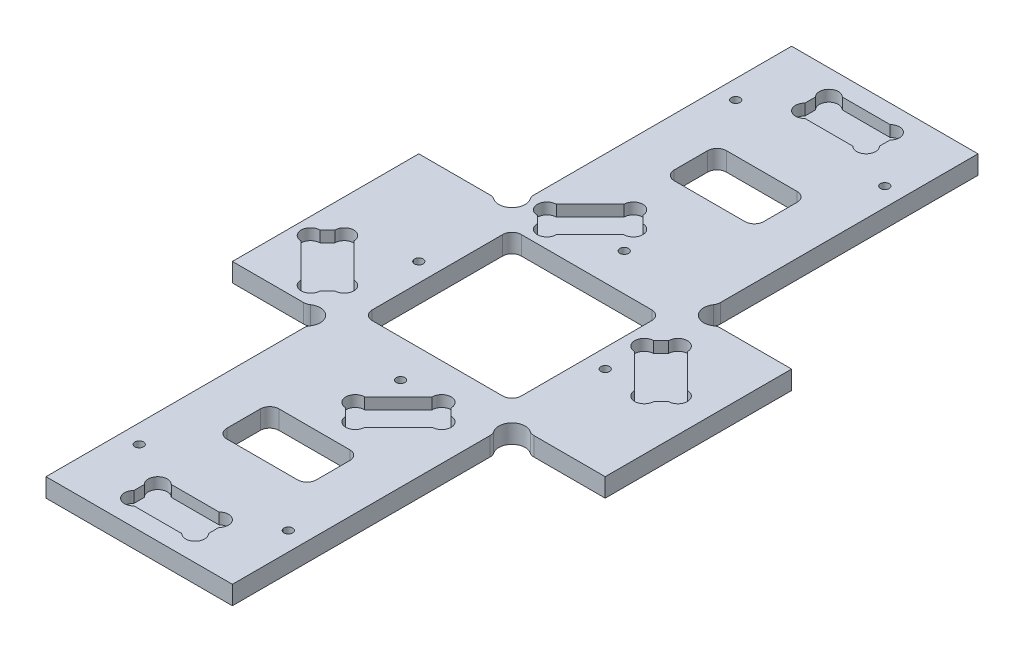
SolidWorks part; units mm, degrees
ref_plane "Front" through (0, 0, 0) normal (0, 0, 1) x (1, 0, 0)
ref_plane "Top" through (0, 0, 0) normal (0, 1, 0) x (1, 0, 0)
ref_plane "Right" through (0, 0, 0) normal (1, 0, 0) x (0, 0, -1)
sketch "Sketch1" plane through (0, 0, 0) normal (0, 1, 0) x (1, 0, 0)
  line L0 (45.4057, 247.3952) -> (45.4057, -6.6048) construction
  line L1 (13.6557, -6.6048) -> (77.1557, -6.6048)
  line L2 (13.6557, -6.6048) -> (13.6557, 247.3952)
  line L3 (13.6557, 247.3952) -> (77.1557, 247.3952)
  line L4 (77.1557, -6.6048) -> (77.1557, 247.3952)
  line L5 (13.6557, 152.1452) -> (-18.0943, 152.1452)
  line L6 (13.6557, 152.1452) -> (13.6557, 88.6452)
  line L7 (13.6557, 88.6452) -> (-18.0943, 88.6452)
  line L8 (-18.0943, 152.1452) -> (-18.0943, 88.6452)
  line L9 (77.1557, 88.6452) -> (108.9057, 88.6452)
  line L10 (108.9057, 152.1452) -> (108.9057, 88.6452)
  line L11 (77.1557, 152.1452) -> (108.9057, 152.1452)
  line L12 (77.1557, 152.1452) -> (77.1557, 88.6452)
  dimension "D1" = 63.5
  dimension "D2" = 254
  dimension "D3" = 31.75
  dimension "D4" = 63.5
  dimension "D5" = 95.25
extrude "Boss-Extrude1" add sketch "Sketch1" along normal blind 6.35 contours L5 L8 L7 L2 | L0 L3 L2 L1 | L3 L0 L1 L4 | L11 L4 L9 L10 region at (61.2807, 0, -120.3952) region at (29.5307, 0, -120.3952) region at (-2.2193, 0, -120.3952) region at (93.0307, 0, -120.3952)
sketch "Sketch2" plane through (0, 6.35, 0) normal (0, 1, 0) x (1, 0, 0)
  line L0 (13.6557, 88.6452) -> (77.1557, 152.1452) construction
  line L1 (77.1557, 152.1452) -> (77.1557, 88.6452) construction
  line L2 (77.1557, 88.6452) -> (45.4057, 120.3952) construction
  line L3 (45.4057, 120.3952) -> (45.4057, 152.1452) construction
  line L4 (45.4057, 152.1452) -> (13.6557, 152.1452) construction
  line L5 (13.6557, 152.1452) -> (45.4057, 120.3952) construction
  line L6 (2.3005, 109.6188) -> (-6.6798, 100.6386) construction
  line L7 (11.2807, 100.6386) -> (-6.6798, 118.5991)
  line L8 (-6.6798, 118.5991) -> (11.2807, 100.6386)
  line L9 (-6.6798, 118.5991) -> (-15.6601, 109.6188)
  line L10 (11.2807, 100.6386) -> (2.3005, 91.6583)
  line L11 (-15.6601, 109.6188) -> (2.3005, 91.6583)
  line L23 (11.2807, 100.6386) -> (2.3005, 91.6583)
  line L28 (43.9231, 166.4458) -> (25.9626, 148.4853)
  line L29 (43.9231, 166.4458) -> (34.9428, 175.4261)
  line L30 (34.9428, 175.4261) -> (16.9823, 157.4655)
  line L31 (25.9626, 148.4853) -> (16.9823, 157.4655)
  line L36 (43.9231, 166.4458) -> (34.9428, 175.4261)
  line L38 (6.7906, 96.1485) -> (-11.1699, 114.109) construction
  line L43 (91.7698, 115.8429) -> (73.8093, 133.8034)
  line L44 (91.7698, 115.8429) -> (100.7501, 124.8232)
  line L45 (100.7501, 124.8232) -> (82.7895, 142.7837)
  line L46 (73.8093, 133.8034) -> (82.7895, 142.7837)
  line L51 (91.7698, 115.8429) -> (100.7501, 124.8232)
  line L58 (41.1669, 67.9962) -> (59.1274, 85.9567)
  line L59 (41.1669, 67.9962) -> (50.1472, 59.0159)
  line L60 (50.1472, 59.0159) -> (68.1077, 76.9765)
  line L61 (59.1274, 85.9567) -> (68.1077, 76.9765)
  line L66 (41.1669, 67.9962) -> (50.1472, 59.0159)
  point P15 (2.3005, 109.6188)
  point P64 (42.545, 117.221)
  dimension "D1" = 22.86
  dimension "D2" = 25.4
  dimension "D3" = 12.7
  dimension "D7" = 38.1
  dimension "D6" = 4
extrude "Cut-Extrude14" cut sketch "Sketch2" against normal blind 3.81 contours L9 L11 L10 L7 | L31 L28 L29 L30 | L46 L43 L44 L45 | L61 L58 L59 L60 region at (-2.1897, 6.35, -105.1287) region at (30.4527, 6.35, -161.9557) region at (87.2797, 6.35, -129.3133) region at (54.6373, 6.35, -72.4863)
sketch "Sketch14" plane through (0, 6.35, 0) normal (0, 1, 0) x (1, 0, 0)
  line L0 (45.4057, -6.6048) -> (45.4057, 247.3952) construction
  line L1 (13.6557, -6.6048) -> (77.1557, -6.6048) construction
  line L2 (13.6557, 247.3952) -> (77.1557, 247.3952) construction
  line L3 (-18.0943, 120.3952) -> (108.9057, 120.3952) construction
  line L4 (32.7057, 241.0452) -> (58.1057, 241.0452)
  line L5 (32.7057, 241.0452) -> (32.7057, 228.3452)
  line L6 (32.7057, 228.3452) -> (58.1057, 228.3452)
  line L7 (58.1057, 241.0452) -> (58.1057, 228.3452)
  line L8 (32.7057, 241.0452) -> (58.1057, 228.3452) construction
  line L9 (32.7057, 228.3452) -> (58.1057, 241.0452) construction
  line L10 (-18.0943, 152.1452) -> (-18.0943, 88.6452) construction
  line L11 (108.9057, 152.1452) -> (108.9057, 88.6452) construction
  line L12 (32.7057, 12.4452) -> (58.1057, 12.4452)
  line L13 (58.1057, -0.2548) -> (58.1057, 12.4452)
  line L14 (32.7057, -0.2548) -> (58.1057, -0.2548)
  line L15 (32.7057, -0.2548) -> (32.7057, 12.4452)
  point P6 (45.4057, 234.6952)
  dimension "D1" = 12.7
  dimension "D2" = 25.4
  dimension "D3" = 6.35
extrude "Cut-Extrude16" cut sketch "Sketch14" against normal blind 3.81
sketch "Sketch15" plane through (0, 6.35, 0) normal (0, 1, 0) x (1, 0, 0)
  line L0 (45.4057, 247.3952) -> (45.4057, -6.6048) construction
  line L1 (13.6557, 247.3952) -> (77.1557, 247.3952) construction
  line L2 (13.6557, -6.6048) -> (77.1557, -6.6048) construction
  line L3 (45.4057, -6.6048) -> (108.9057, 120.3952) construction
  line L4 (108.9057, 152.1452) -> (108.9057, 88.6452) construction
  line L5 (108.9057, 120.3952) -> (-18.0943, 120.3952) construction
  line L6 (-18.0943, 152.1452) -> (-18.0943, 88.6452) construction
  line L7 (30.1657, 35.3052) -> (60.6457, 35.3052)
  line L8 (20.0057, 94.9952) -> (70.8057, 94.9952)
  line L9 (20.0057, 94.9952) -> (20.0057, 145.7952)
  line L10 (20.0057, 145.7952) -> (70.8057, 145.7952)
  line L11 (70.8057, 94.9952) -> (70.8057, 145.7952)
  line L12 (20.0057, 94.9952) -> (70.8057, 145.7952) construction
  line L13 (20.0057, 145.7952) -> (70.8057, 94.9952) construction
  line L14 (30.1657, 187.7052) -> (60.6457, 187.7052)
  line L15 (30.1657, 187.7052) -> (30.1657, 205.4852)
  line L16 (30.1657, 205.4852) -> (60.6457, 205.4852)
  line L17 (60.6457, 187.7052) -> (60.6457, 205.4852)
  line L18 (30.1657, 187.7052) -> (60.6457, 205.4852) construction
  line L19 (30.1657, 205.4852) -> (60.6457, 187.7052) construction
  line L20 (60.6457, 53.0852) -> (60.6457, 35.3052)
  line L21 (30.1657, 53.0852) -> (60.6457, 53.0852)
  line L22 (30.1657, 53.0852) -> (30.1657, 35.3052)
  point P6 (45.4057, 120.3952)
  point P17 (45.4057, 196.5952)
  dimension "D1" = 50.8
  dimension "D2" = 50.8
  dimension "D3" = 17.78
  dimension "D4" = 30.48
  dimension "D5" = 50.8
extrude "Cut-Extrude17" cut sketch "Sketch15" against normal through all
fillet "Fillet1" radius 3.175 12 edges at (30.1657, 3.175, -205.4852) (30.1657, 3.175, -187.7052) (60.6457, 3.175, -187.7052) (60.6457, 3.175, -205.4852) (60.6457, 3.175, -53.0852) (30.1657, 3.175, -53.0852) (30.1657, 3.175, -35.3052) (60.6457, 3.175, -35.3052) (70.8057, 3.175, -94.9952) (70.8057, 3.175, -145.7952) (20.0057, 3.175, -145.7952) (20.0057, 3.175, -94.9952)
sketch "Sketch16" plane through (0, 6.35, 0) normal (0, 1, 0) x (1, 0, 0)
  line L0 (45.4057, -6.6048) -> (45.4057, 247.3952) construction
  line L1 (13.6557, 88.6452) -> (10.4807, 88.6452)
  line L2 (13.6557, 88.6452) -> (13.6557, 85.4702)
  line L3 (13.6557, 85.4702) -> (10.4807, 85.4702)
  line L4 (10.4807, 88.6452) -> (10.4807, 85.4702)
  line L5 (13.6557, -6.6048) -> (77.1557, -6.6048) construction
  line L6 (13.6557, 247.3952) -> (77.1557, 247.3952) construction
  line L7 (45.4057, 247.3952) -> (108.9057, 120.3952) construction
  line L8 (108.9057, 152.1452) -> (108.9057, 88.6452) construction
  line L9 (108.9057, 120.3952) -> (-18.0943, 120.3952) construction
  line L10 (-18.0943, 152.1452) -> (-18.0943, 88.6452) construction
  line L11 (77.1557, 85.4702) -> (80.3307, 85.4702)
  line L12 (80.3307, 88.6452) -> (80.3307, 85.4702)
  line L13 (77.1557, 88.6452) -> (80.3307, 88.6452)
  line L14 (77.1557, 88.6452) -> (77.1557, 85.4702)
  line L16 (77.1557, 152.1452) -> (77.1557, 155.3202)
  line L17 (77.1557, 152.1452) -> (80.3307, 152.1452)
  line L18 (80.3307, 152.1452) -> (80.3307, 155.3202)
  line L19 (77.1557, 155.3202) -> (80.3307, 155.3202)
  line L20 (13.6557, 155.3202) -> (10.4807, 155.3202)
  line L21 (10.4807, 152.1452) -> (10.4807, 155.3202)
  line L22 (13.6557, 152.1452) -> (10.4807, 152.1452)
  line L23 (13.6557, 152.1452) -> (13.6557, 155.3202)
  circle A0 centre (10.4807, 85.4702) radius 4.4901
  circle A1 centre (80.3307, 85.4702) radius 4.4901
  circle A2 centre (80.3307, 155.3202) radius 4.4901
  circle A3 centre (10.4807, 155.3202) radius 4.4901
  dimension "D1" = 3.175
  dimension "D2" = 3.175
extrude "Cut-Extrude18" cut sketch "Sketch16" against normal through all contours L1 A0 L2 L3 L4 | L1 L4 L3 L2 | L13 L14 L11 L12 | L14 A1 L13 L12 L11 | L19 L16 L17 L18 | L17 A2 L16 L19 L18 | L22 L23 L20 L21 | L23 A3 L22 L21 L20 region at (12.0682, 6.35, -87.0577) region at (10.1802, 6.35, -85.1697) region at (78.7432, 6.35, -87.0577) region at (80.6312, 6.35, -85.1697) region at (78.7432, 6.35, -153.7327) region at (80.6312, 6.35, -155.6206) region at (12.0682, 6.35, -153.7327) region at (10.1802, 6.35, -155.6206)
fillet "Fillet2" radius 3.175 8 edges at (13.6557, 3.175, -158.4952) (7.3057, 3.175, -152.1452) (77.1557, 3.175, -158.4952) (83.5057, 3.175, -152.1452) (77.1557, 3.175, -82.2952) (83.5057, 3.175, -88.6452) (13.6557, 3.175, -82.2952) (7.3057, 3.175, -88.6452)
sketch "Sketch17" plane through (0, 6.35, 0) normal (0, 1, 0) x (1, 0, 0)
  line L0 (45.4057, -6.6048) -> (45.4057, 247.3952) construction
  line L1 (13.6557, -6.6048) -> (77.1557, -6.6048) construction
  line L2 (13.6557, 247.3952) -> (77.1557, 247.3952) construction
  line L3 (45.4057, 247.3952) -> (108.9057, 120.3952) construction
  line L4 (108.9057, 152.1452) -> (108.9057, 88.6452) construction
  line L5 (108.9057, 120.3952) -> (-18.0943, 120.3952) construction
  line L6 (-18.0943, 152.1452) -> (-18.0943, 88.6452) construction
  line L7 (-18.0943, 120.3952) -> (32.7057, 6.0952) construction
  line L8 (32.7057, 12.4452) -> (32.7057, -0.2548) construction
  line L9 (32.7057, 6.0952) -> (58.1057, 6.0952) construction
  line L10 (58.1057, -0.2548) -> (58.1057, 12.4452) construction
  line L11 (32.7057, 12.4452) -> (34.9917, 12.4452)
  line L12 (32.7057, 12.4452) -> (32.7057, 10.1592)
  line L13 (34.9917, 12.4452) -> (34.9917, 10.1592)
  line L14 (32.7057, 10.1592) -> (34.9917, 10.1592)
  line L15 (58.1057, 12.4452) -> (32.7057, 12.4452) construction
  line L16 (34.9917, -0.2548) -> (34.9917, 2.0312)
  line L17 (32.7057, 2.0312) -> (34.9917, 2.0312)
  line L18 (32.7057, -0.2548) -> (32.7057, 2.0312)
  line L19 (32.7057, -0.2548) -> (34.9917, -0.2548)
  line L20 (58.1057, -0.2548) -> (55.8197, -0.2548)
  line L21 (58.1057, -0.2548) -> (58.1057, 2.0312)
  line L22 (58.1057, 2.0312) -> (55.8197, 2.0312)
  line L23 (55.8197, -0.2548) -> (55.8197, 2.0312)
  line L24 (55.8197, 12.4452) -> (55.8197, 10.1592)
  line L25 (58.1057, 10.1592) -> (55.8197, 10.1592)
  line L26 (58.1057, 12.4452) -> (58.1057, 10.1592)
  line L27 (58.1057, 12.4452) -> (55.8197, 12.4452)
  line L28 (58.1057, 241.0452) -> (58.1057, 238.7592)
  line L29 (58.1057, 238.7592) -> (55.8197, 238.7592)
  line L30 (55.8197, 241.0452) -> (55.8197, 238.7592)
  line L31 (58.1057, 241.0452) -> (55.8197, 241.0452)
  line L32 (58.1057, 228.3452) -> (55.8197, 228.3452)
  line L33 (58.1057, 228.3452) -> (58.1057, 230.6312)
  line L34 (58.1057, 230.6312) -> (55.8197, 230.6312)
  line L35 (55.8197, 228.3452) -> (55.8197, 230.6312)
  line L36 (34.9917, 228.3452) -> (34.9917, 230.6312)
  line L37 (32.7057, 230.6312) -> (34.9917, 230.6312)
  line L38 (32.7057, 228.3452) -> (32.7057, 230.6312)
  line L39 (32.7057, 228.3452) -> (34.9917, 228.3452)
  line L40 (32.7057, 241.0452) -> (34.9917, 241.0452)
  line L41 (32.7057, 241.0452) -> (32.7057, 238.7592)
  line L42 (32.7057, 238.7592) -> (34.9917, 238.7592)
  line L43 (34.9917, 241.0452) -> (34.9917, 238.7592)
  circle A0 centre (34.9917, 10.1592) radius 3.2329
  circle A1 centre (34.9917, 2.0312) radius 3.2329
  circle A2 centre (55.8197, 2.0312) radius 3.2329
  circle A3 centre (55.8197, 10.1592) radius 3.2329
  circle A4 centre (55.8197, 238.7592) radius 3.2329
  circle A5 centre (55.8197, 230.6312) radius 3.2329
  circle A6 centre (34.9917, 230.6312) radius 3.2329
  circle A7 centre (34.9917, 238.7592) radius 3.2329
  dimension "D1" = 2.286
  dimension "D2" = 2.286
extrude "Cut-Extrude19" cut sketch "Sketch17" against normal blind 3.81 contours L43 L40 L41 L42 | L41 A7 L40 L43 L42 | L31 A4 L28 L29 L30 | L28 L31 L30 L29 | L33 A5 L32 L35 L34 | L35 L32 L33 L34 | L39 A6 L38 L37 L36 | L38 L39 L36 L37 | L19 A1 L18 L17 L16 | L18 L19 L16 L17 | L12 A0 L11 L13 L14 | L12 L14 L13 L11 | L27 A3 L26 L25 L24 | L26 L27 L24 L25 | L21 A2 L20 L23 L22 | L23 L20 L21 L22 region at (33.8487, 6.35, -11.3022) region at (35.208, 6.35, -9.9428) region at (33.8487, 6.35, -0.8882) region at (35.208, 6.35, -2.2475) region at (56.9627, 6.35, -0.8882) region at (55.6033, 6.35, -2.2475) region at (56.9627, 6.35, -11.3022) region at (55.6033, 6.35, -9.9428) region at (56.9627, 6.35, -239.9022) region at (55.6033, 6.35, -238.5428) region at (56.9627, 6.35, -229.4882) region at (55.6033, 6.35, -230.8475) region at (33.8487, 6.35, -229.4882) region at (35.208, 6.35, -230.8475) region at (33.8487, 6.35, -239.9022) region at (35.208, 6.35, -238.5428)
sketch "Sketch18" plane through (0, 6.35, 0) normal (0, 1, 0) x (1, 0, 0)
  line L0 (-15.6601, 109.6188) -> (-14.0436, 111.2353)
  line L1 (-15.6601, 109.6188) -> (-14.0436, 108.0024)
  line L2 (-14.0436, 111.2353) -> (-12.4272, 109.6188)
  line L3 (-14.0436, 108.0024) -> (-12.4272, 109.6188)
  line L4 (-6.6798, 118.5991) -> (-15.6601, 109.6188) construction
  line L5 (-11.1699, 114.109) -> (6.7906, 96.1485) construction
  line L6 (11.2807, 100.6386) -> (2.3005, 91.6583) construction
  line L7 (6.7906, 96.1485) -> (2.3005, 109.6188) construction
  line L8 (11.2807, 100.6386) -> (-6.6798, 118.5991) construction
  line L9 (2.3005, 109.6188) -> (-6.6798, 100.6386) construction
  line L10 (-15.6601, 109.6188) -> (2.3005, 91.6583) construction
  line L11 (-8.2962, 116.9827) -> (-6.6798, 115.3662)
  line L12 (-5.0634, 116.9827) -> (-6.6798, 115.3662)
  line L13 (-6.6798, 118.5991) -> (-5.0634, 116.9827)
  line L14 (-6.6798, 118.5991) -> (-8.2962, 116.9827)
  line L15 (11.2807, 100.6386) -> (9.6643, 99.0221)
  line L16 (11.2807, 100.6386) -> (9.6643, 102.255)
  line L17 (9.6643, 102.255) -> (8.0478, 100.6386)
  line L18 (9.6643, 99.0221) -> (8.0478, 100.6386)
  line L19 (3.9169, 93.2748) -> (2.3005, 94.8912)
  line L20 (0.684, 93.2748) -> (2.3005, 94.8912)
  line L21 (2.3005, 91.6583) -> (0.684, 93.2748)
  line L22 (2.3005, 91.6583) -> (3.9169, 93.2748)
  line L23 (45.4057, 145.7952) -> (45.4057, 94.9952) construction
  line L24 (67.6307, 145.7952) -> (23.1807, 145.7952) construction
  line L25 (23.1807, 94.9952) -> (67.6307, 94.9952) construction
  line L26 (45.4057, 94.9952) -> (70.8057, 120.3952) construction
  line L27 (70.8057, 98.1702) -> (70.8057, 142.6202) construction
  line L28 (70.8057, 120.3952) -> (20.0057, 120.3952) construction
  line L29 (20.0057, 142.6202) -> (20.0057, 98.1702) construction
  circle A0 centre (-12.4272, 109.6188) radius 3.2329
  circle A1 centre (-6.6798, 115.3662) radius 3.2329
  circle A2 centre (8.0478, 100.6386) radius 3.2329
  circle A3 centre (2.3005, 94.8912) radius 3.2329
  dimension "D1" = 2.286
  dimension "D2" = 2.286
extrude "Cut-Extrude20" cut sketch "Sketch18" against normal blind 3.81 contours L1 L3 L2 L0 | L1 A0 L0 L2 L3 | L13 L14 L11 L12 | L14 A1 L13 L12 L11 | L18 L15 L16 L17 | L16 A2 L15 L18 L17 | L21 L22 L19 L20 | L22 A3 L21 L20 L19 region at (-14.0436, 6.35, -109.6188) region at (-12.1212, 6.35, -109.6188) region at (-6.6798, 6.35, -116.9827) region at (-6.6798, 6.35, -115.0602) region at (9.6643, 6.35, -100.6386) region at (7.7419, 6.35, -100.6386) region at (2.3005, 6.35, -93.2748) region at (2.3005, 6.35, -95.1972)
sketch "Sketch19" plane through (0, 6.35, 0) normal (0, 1, 0) x (1, 0, 0)
  line L0 (34.9428, 175.4261) -> (33.3264, 173.8096)
  line L1 (34.9428, 175.4261) -> (36.5593, 173.8096)
  line L2 (33.3264, 173.8096) -> (34.9428, 172.1932)
  line L3 (36.5593, 173.8096) -> (34.9428, 172.1932)
  line L4 (43.9231, 166.4458) -> (34.9428, 175.4261) construction
  line L5 (34.9428, 175.4261) -> (16.9823, 157.4655) construction
  line L6 (39.433, 170.9359) -> (21.4725, 152.9754) construction
  line L7 (25.9626, 148.4853) -> (16.9823, 157.4655) construction
  line L8 (25.9626, 166.4458) -> (34.9428, 157.4655) construction
  line L9 (43.9231, 166.4458) -> (25.9626, 148.4853) construction
  line L11 (42.3067, 164.8294) -> (40.6902, 166.4458)
  line L12 (42.3067, 168.0622) -> (40.6902, 166.4458)
  line L13 (43.9231, 166.4458) -> (42.3067, 168.0622)
  line L14 (43.9231, 166.4458) -> (42.3067, 164.8294)
  line L15 (25.9626, 148.4853) -> (27.579, 150.1017)
  line L16 (25.9626, 148.4853) -> (24.3461, 150.1017)
  line L17 (24.3461, 150.1017) -> (25.9626, 151.7182)
  line L18 (27.579, 150.1017) -> (25.9626, 151.7182)
  line L19 (18.5988, 159.082) -> (20.2152, 157.4655)
  line L20 (18.5988, 155.8491) -> (20.2152, 157.4655)
  line L21 (16.9823, 157.4655) -> (18.5988, 155.8491)
  line L22 (16.9823, 157.4655) -> (18.5988, 159.082)
  line L23 (82.7895, 142.7837) -> (81.1731, 141.1672)
  line L24 (82.7895, 142.7837) -> (84.406, 141.1672)
  line L25 (81.1731, 141.1672) -> (82.7895, 139.5508)
  line L26 (84.406, 141.1672) -> (82.7895, 139.5508)
  line L27 (73.8093, 133.8034) -> (82.7895, 142.7837) construction
  line L28 (78.2994, 138.2935) -> (96.2599, 120.333) construction
  line L29 (91.7698, 115.8429) -> (100.7501, 124.8232) construction
  line L30 (91.7698, 133.8034) -> (82.7895, 124.8232) construction
  line L34 (75.4257, 135.4199) -> (77.0422, 133.8034)
  line L35 (75.4257, 132.187) -> (77.0422, 133.8034)
  line L36 (73.8093, 133.8034) -> (75.4257, 132.187)
  line L37 (73.8093, 133.8034) -> (75.4257, 135.4199)
  line L38 (100.7501, 124.8232) -> (82.7895, 142.7837) construction
  line L39 (91.7698, 115.8429) -> (73.8093, 133.8034) construction
  line L40 (99.1336, 123.2067) -> (97.5172, 124.8232)
  line L41 (99.1336, 126.4396) -> (97.5172, 124.8232)
  line L42 (100.7501, 124.8232) -> (99.1336, 126.4396)
  line L43 (100.7501, 124.8232) -> (99.1336, 123.2067)
  line L44 (91.7698, 115.8429) -> (93.3862, 117.4593)
  line L45 (91.7698, 115.8429) -> (90.1534, 117.4593)
  line L46 (90.1534, 117.4593) -> (91.7698, 119.0758)
  line L47 (93.3862, 117.4593) -> (91.7698, 119.0758)
  line L48 (45.657, 63.5061) -> (63.6175, 81.4666) construction
  line L49 (41.1669, 67.9962) -> (50.1472, 59.0159) construction
  line L50 (59.1274, 85.9567) -> (68.1077, 76.9765) construction
  line L51 (50.1472, 76.9765) -> (59.1274, 67.9962) construction
  line L52 (41.1669, 67.9962) -> (59.1274, 85.9567) construction
  line L53 (50.1472, 59.0159) -> (68.1077, 76.9765) construction
  line L54 (41.1669, 67.9962) -> (42.7833, 69.6126)
  line L55 (41.1669, 67.9962) -> (42.7833, 66.3798)
  line L56 (42.7833, 69.6126) -> (44.3998, 67.9962)
  line L57 (42.7833, 66.3798) -> (44.3998, 67.9962)
  line L59 (51.7636, 60.6324) -> (50.1472, 62.2488)
  line L60 (48.5307, 60.6324) -> (50.1472, 62.2488)
  line L61 (50.1472, 59.0159) -> (48.5307, 60.6324)
  line L62 (50.1472, 59.0159) -> (51.7636, 60.6324)
  line L63 (68.1077, 76.9765) -> (66.4912, 75.36)
  line L64 (68.1077, 76.9765) -> (66.4912, 78.5929)
  line L65 (66.4912, 78.5929) -> (64.8748, 76.9765)
  line L66 (66.4912, 75.36) -> (64.8748, 76.9765)
  line L67 (57.511, 84.3403) -> (59.1274, 82.7238)
  line L68 (60.7439, 84.3403) -> (59.1274, 82.7238)
  line L69 (59.1274, 85.9567) -> (60.7439, 84.3403)
  line L70 (59.1274, 85.9567) -> (57.511, 84.3403)
  circle A0 centre (34.9428, 172.1932) radius 3.2329
  circle A1 centre (40.6902, 166.4458) radius 3.2329
  circle A2 centre (25.9626, 151.7182) radius 3.2329
  circle A3 centre (20.2152, 157.4655) radius 3.2329
  circle A4 centre (82.7895, 139.5508) radius 3.2329
  circle A5 centre (77.0422, 133.8034) radius 3.2329
  circle A6 centre (97.5172, 124.8232) radius 3.2329
  circle A7 centre (91.7698, 119.0758) radius 3.2329
  circle A8 centre (44.3998, 67.9962) radius 3.2329
  circle A9 centre (50.1472, 62.2488) radius 3.2329
  circle A10 centre (64.8748, 76.9765) radius 3.2329
  circle A11 centre (59.1274, 82.7238) radius 3.2329
  dimension "D1" = 2.286
  dimension "D2" = 2.286
  dimension "D3" = 2.286
  dimension "D4" = 2.286
  dimension "D5" = 2.286
  dimension "D6" = 2.286
extrude "Cut-Extrude22" cut sketch "Sketch19" against normal blind 3.81 contours L55 A8 L54 L56 L57 | L61 L62 L59 L60 | L62 A9 L61 L60 L59 | L69 L70 L67 L68 | L70 A11 L69 L68 L67 | L66 L63 L64 L65 | L64 A10 L63 L66 L65 | L44 L47 L46 L45 | L44 A7 L45 L46 L47 | L43 L42 L41 L40 | L42 A6 L43 L40 L41 | L26 L24 L23 L25 | L23 A4 L24 L26 L25 | L37 L36 L35 L34 | L36 A5 L37 L34 L35 | L15 A2 L16 L17 L18 | L15 L18 L17 L16 | L22 L21 L20 L19 | L21 A3 L22 L19 L20 | L3 L1 L0 L2 | L0 A0 L1 L3 L2 | L14 L13 L12 L11 | L13 A1 L14 L11 L12 | L55 L57 L56 L54 | L56 L57 L55 L54 | L18 L17 L16 L15 region at (34.9428, 6.35, -173.8096) region at (34.9428, 6.35, -171.8872) region at (40.3842, 6.35, -166.4458) region at (42.3067, 6.35, -166.4458) region at (25.9626, 6.35, -150.1017) region at (25.9626, 6.35, -152.0241) region at (20.5212, 6.35, -157.4655) region at (18.5988, 6.35, -157.4655) region at (82.7895, 6.35, -141.1672) region at (82.7895, 6.35, -139.2448) region at (77.3481, 6.35, -133.8034) region at (75.4257, 6.35, -133.8034) region at (97.2112, 6.35, -124.8232) region at (99.1336, 6.35, -124.8232) region at (91.7698, 6.35, -117.4593) region at (91.7698, 6.35, -119.3818) region at (42.7833, 6.35, -67.9962) region at (44.7058, 6.35, -67.9962) region at (50.1472, 6.35, -60.6324) region at (50.1472, 6.35, -62.5548) region at (66.4912, 6.35, -76.9765) region at (64.5688, 6.35, -76.9765) region at (59.1274, 6.35, -84.3403) region at (59.1274, 6.35, -82.4179)
sketch "Sketch20" plane through (0, 6.35, 0) normal (0, 1, 0) x (1, 0, 0)
  line L0 (45.4057, 247.3952) -> (45.4057, -6.6048) construction
  line L1 (13.6557, 247.3952) -> (77.1557, 247.3952) construction
  line L2 (13.6557, -6.6048) -> (77.1557, -6.6048) construction
  line L3 (45.4057, -6.6048) -> (108.9057, 120.3952) construction
  line L4 (108.9057, 152.1452) -> (108.9057, 88.6452) construction
  line L5 (108.9057, 120.3952) -> (-18.0943, 120.3952) construction
  line L6 (-18.0943, 152.1452) -> (-18.0943, 88.6452) construction
  circle A0 centre (20.0057, 221.9952) radius 1.4732
  circle A1 centre (70.8057, 221.9952) radius 1.4732
  circle A2 centre (70.8057, 18.7952) radius 1.4732
  circle A3 centre (20.0057, 18.7952) radius 1.4732
  circle A4 centre (13.6557, 120.3952) radius 1.4732
  circle A5 centre (77.1557, 120.3952) radius 1.4732
  dimension "D1" = 2.9464
  dimension "D2" = 25.4
  dimension "D3" = 25.4
  dimension "D4" = 2.9464
  dimension "D5" = 31.75
extrude "Cut-Extrude23" cut sketch "Sketch20" against normal through all and the other way through all
sketch "Sketch21" plane through (0, 6.35, 0) normal (0, 1, 0) x (1, 0, 0)
  line L0 (13.6557, 247.3952) -> (77.1557, 247.3952) construction
  line L1 (-18.0943, 120.3952) -> (108.9057, 120.3952) construction
  line L2 (-18.0943, 152.1452) -> (-18.0943, 88.6452) construction
  line L3 (108.9057, 152.1452) -> (108.9057, 88.6452) construction
  circle A0 centre (45.5421, 158.4952) radius 1.4732
  circle A1 centre (45.5421, 82.2952) radius 1.4732
  point P0 (45.5421, 158.4952)
  point P11 (0, 0)
  dimension "D2" = 2.9464
  dimension "D1" = 88.9
extrude "Cut-Extrude24" cut sketch "Sketch21" against normal through all
